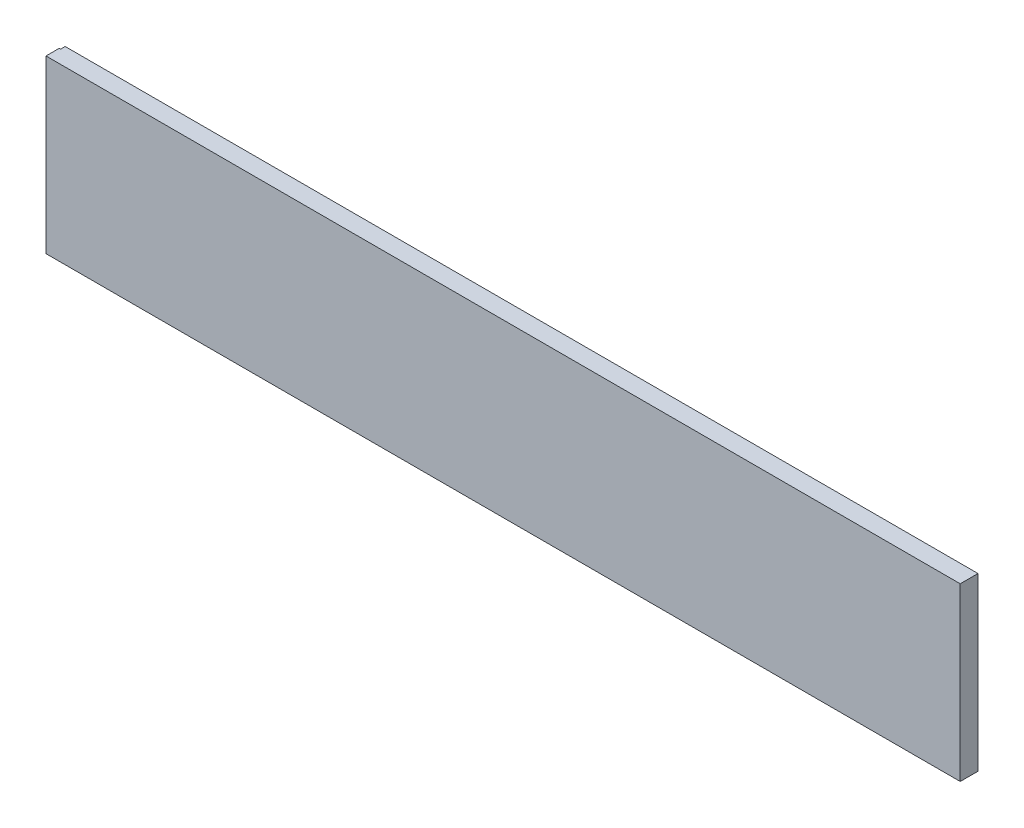
SolidWorks part; units mm, degrees
ref_plane "Front Plane" through (0, 0, 0) normal (0, 0, 1) x (1, 0, 0)
ref_plane "Top Plane" through (0, 0, 0) normal (0, 1, 0) x (1, 0, 0)
ref_plane "Right Plane" through (0, 0, 0) normal (1, 0, 0) x (0, 0, -1)
sketch "Sketch1" plane through (0, 0, 0) normal (0, 0, 1) x (1, 0, 0)
  line L0 (0, 0) -> (0, 152.64) construction
  line L1 (-406.4, -152.64) -> (406.4, -152.64)
  line L2 (-406.4, -152.64) -> (-406.4, 152.64)
  line L5 (-406.4, -152.64) -> (406.4, 152.64) construction
  line L6 (-406.4, 152.64) -> (406.4, -152.64) construction
  line L7 (0, 152.64) -> (0, 95.04)
  line L8 (0, 0) -> (406.4, 0) construction
  line L9 (-406.4, 152.64) -> (-406.4, 232.64)
  line L10 (-406.4, 232.64) -> (1650.5081, 232.64)
  line L11 (406.4, -152.64) -> (1650.5081, -152.64)
  line L12 (1650.5081, -152.64) -> (1650.5081, 232.64)
  circle A0 centre (0, 0) radius 36
  point P0 (0, 0)
extrude "Boss-Extrude1" add sketch "Sketch1" along normal blind 20 contours L2 L1 A0 region at (625.2664, 40.2066, 0)
sketch "Sketch2" plane through (0, 0, 20) normal (0, 0, 1) x (1, 0, 0)
  line L0 (-406.4, 232.64) -> (-406.4, -152.64)
  line L1 (-406.4, -152.64) -> (1650.5081, -152.64)
  line L2 (1650.5081, -152.64) -> (1650.5081, 232.64)
  line L3 (1650.5081, 232.64) -> (-406.4, 232.64)
extrude "Boss-Extrude2" add sketch "Sketch2" along normal blind 10
sketch "Sketch3" plane through (0, 0, 20) normal (0, 0, -1) x (-1, 0, 0)
  circle A0 centre (0, 0) radius 36
extrude "Boss-Extrude3" add sketch "Sketch3" along normal blind 30
sketch "Sketch4" plane through (0, 0, 0) normal (0, 0, -1) x (-1, 0, 0)
  line L0 (-1650.5081, 232.64) -> (-1650.5081, -152.64)
  line L1 (-1650.5081, 232.64) -> (403.2337, 232.64)
  line L2 (-1650.5081, -152.64) -> (403.2337, -152.64)
  line L3 (403.2337, 232.64) -> (403.2337, -152.64)
  line L4 (406.4, -152.64) -> (-1650.5081, -152.64) construction
  line L5 (-1650.5081, -152.64) -> (-1650.5081, 232.64) construction
  line L6 (-1650.5081, 232.64) -> (-1630.5081, 232.64)
  line L7 (-1630.5081, 212.64) -> (-1630.5081, -143.7511)
  line L8 (-1630.5081, -143.7511) -> (-1630.5081, -132.64)
  line L9 (-1630.5081, -132.64) -> (382.5348, -132.64)
  line L11 (382.5348, -132.64) -> (382.5348, 212.64)
  line L13 (382.5348, 212.64) -> (-1630.5081, 212.64)
  line M7 (-1650.5081, -152.64) -> (406.4, -152.64)
  line M9 (406.4, 232.64) -> (-1650.5081, 232.64)
  line M10 (-1650.5081, 232.64) -> (-1650.5081, -152.64)
extrude "Boss-Extrude4" add sketch "Sketch4" along normal blind 10 contours L3 L1 L13 L11 L9 L7 M9 M10 M7 region at (1640.5081, 211.7443, 0)
